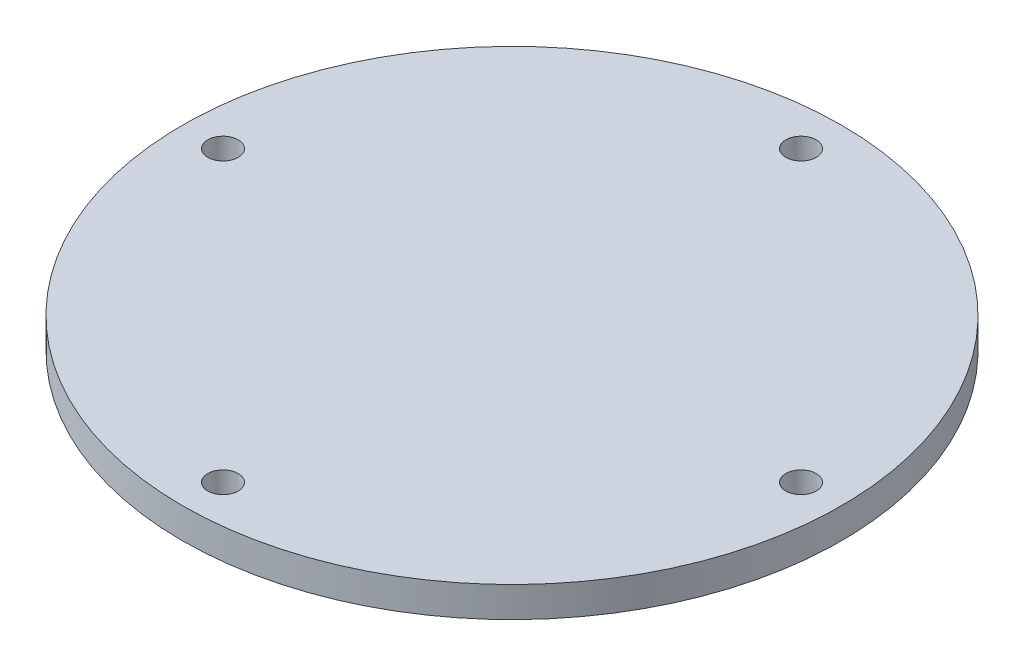
SolidWorks part; units mm, degrees
ref_plane "Front Plane" through (0, 0, 0) normal (0, 0, 1) x (1, 0, 0)
ref_plane "Top Plane" through (0, 0, 0) normal (0, 1, 0) x (1, 0, 0)
ref_plane "Right Plane" through (0, 0, 0) normal (1, 0, 0) x (0, 0, -1)
sketch "Sketch1" plane through (0, 0, 0) normal (0, 1, 0) x (1, 0, 0)
  circle A0 centre (0, 0) radius 32.5
  circle A1 centre (-28.5, 0) radius 1.5
  circle A2 centre (0, 0) radius 28.5 construction
  circle A3 centre (0, 28.5) radius 1.5
  circle A4 centre (28.5, 0) radius 1.5
  circle A5 centre (0, -28.5) radius 1.5
  point P15 (0, 0)
  dimension "D1" = 65
  dimension "D2" = 4
  dimension "D3" = 3
  dimension "D4" = 4
extrude "Boss-Extrude1" add sketch "Sketch1" along normal blind 3
